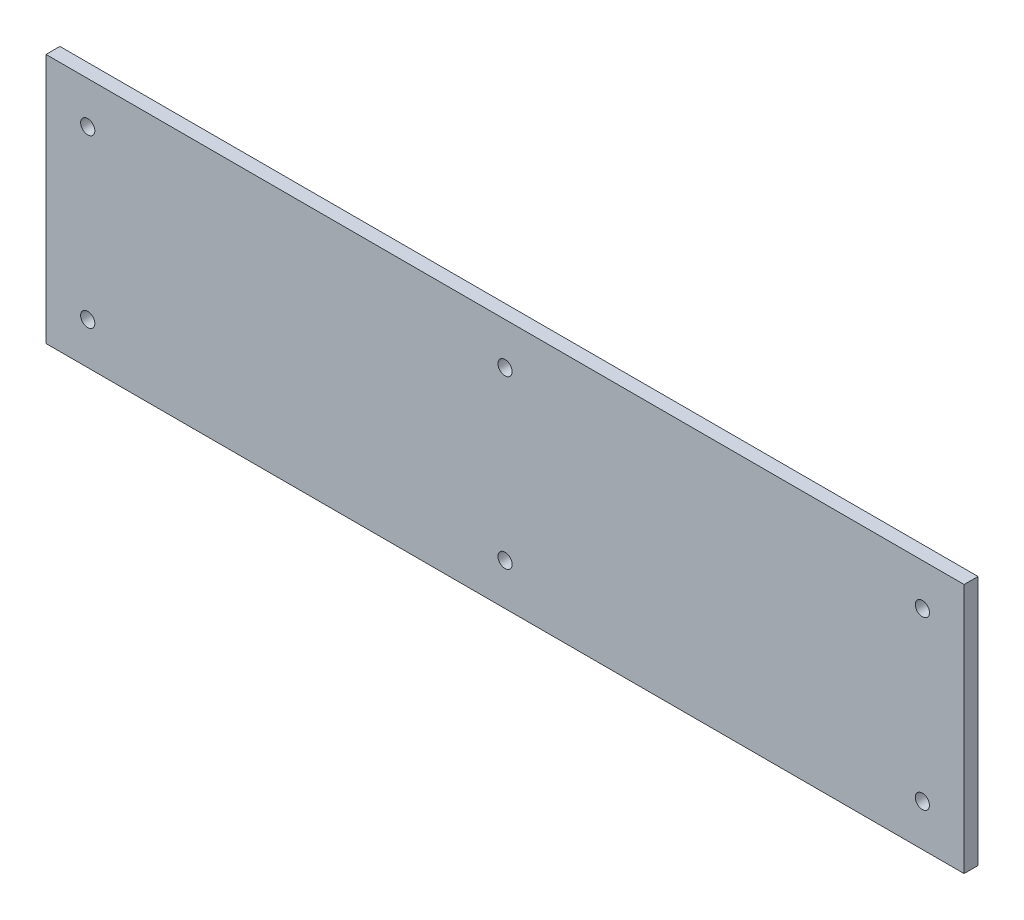
SolidWorks part; units mm, degrees
ref_plane "Front Plane" through (0, 0, 0) normal (0, 0, 1) x (1, 0, 0)
ref_plane "Top Plane" through (0, 0, 0) normal (0, 1, 0) x (1, 0, 0)
ref_plane "Right Plane" through (0, 0, 0) normal (1, 0, 0) x (0, 0, -1)
sketch "Sketch1" plane through (0, 0, 0) normal (0, 0, 1) x (1, 0, 0)
  line L1 (-165, -45) -> (165, -45)
  line L2 (-165, -45) -> (-165, 45)
  line L3 (-165, 45) -> (165, 45)
  line L4 (165, -45) -> (165, 45)
  line L5 (-165, -45) -> (165, 45) construction
  line L6 (-165, 45) -> (165, -45) construction
  point P0 (0, 0)
  dimension "D1" = 330
  dimension "D2" = 90
extrude "Boss-Extrude1" add sketch "Sketch1" along normal mid plane 5
sketch "Sketch2" plane through (0, 0, 2.5) normal (0, 0, 1) x (1, 0, 0)
  line L3 (165, 30) -> (-165, 30)
  line L4 (165, 30) -> (-165, 30) construction
  line L6 (-150, 45) -> (-150, -45)
  line L7 (-150, 45) -> (-150, -45) construction
  line L9 (-165, -30) -> (165, -30)
  line L10 (-165, -30) -> (165, -30) construction
  line L11 (0, 45) -> (0, -45) construction
  line L12 (150, -45) -> (150, 45)
  line L13 (150, -45) -> (150, 45) construction
  line L14 (165, 45) -> (-165, 45) construction
  line L15 (-165, -45) -> (165, -45) construction
  circle A0 centre (150, 30) radius 2.55
  circle A1 centre (150, -30) radius 2.55
  circle A2 centre (0, 30) radius 2.55
  circle A3 centre (0, -30) radius 2.55
  circle A4 centre (-150, -30) radius 2.55
  circle A5 centre (-150, 30) radius 2.55
  dimension "D5" = 5.1
  dimension "D6" = 5.1
  dimension "D7" = 5.1
  dimension "D8" = 5.1
  dimension "D9" = 5.1
  dimension "D10" = 5.1
  dimension "D1" = 15
  dimension "D2" = 15
  dimension "D3" = 15
  dimension "D4" = 15
extrude "Cut-Extrude1" cut sketch "Sketch2" against normal through all
